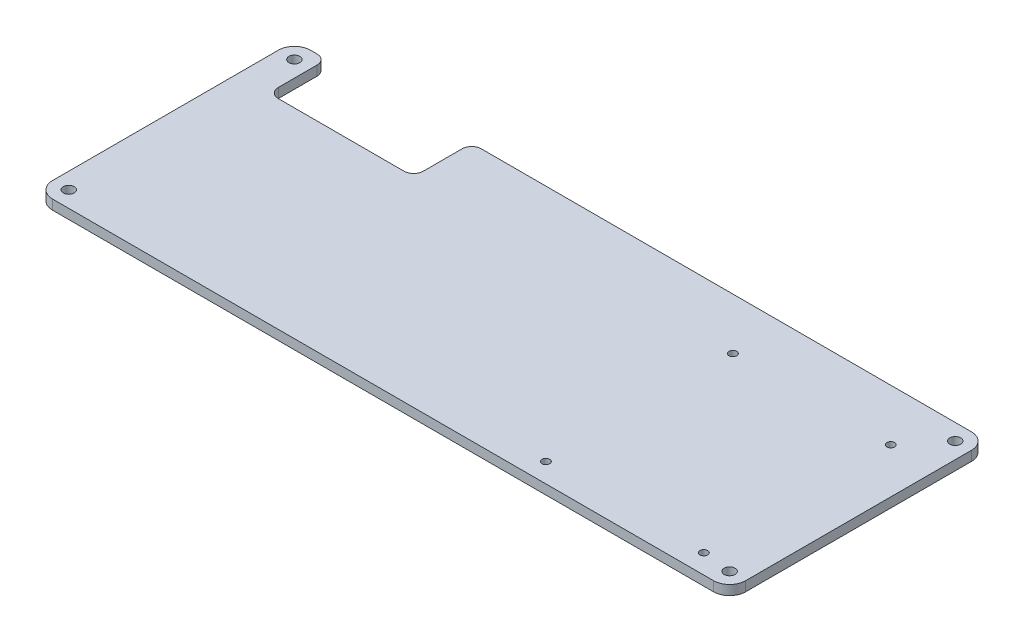
SolidWorks part; units mm, degrees
ref_plane "Front" through (0, 0, 0) normal (0, 0, 1) x (1, 0, 0)
ref_plane "Top" through (0, 0, 0) normal (0, 1, 0) x (1, 0, 0)
ref_plane "Right" through (0, 0, 0) normal (1, 0, 0) x (0, 0, -1)
sketch "Esquisse1" plane through (0, 0, 0) normal (0, 1, 0) x (1, 0, 0)
  line L1 (0, 0) -> (215, 0)
  line L2 (0, 0) -> (0, 80)
  line L3 (0, 80) -> (215, 80)
  line L4 (215, 0) -> (215, 80)
  dimension "D1" = 215
  dimension "D2" = 80
extrude "Boss.-Extru.1" add sketch "Esquisse1" along normal blind 3
fillet "Congé1" radius 5 4 edges at (0, 1.5, -80) (0, 1.5, 0) (215, 1.5, -80) (215, 1.5, 0)
sketch "Esquisse2" plane through (0, 3, 0) normal (0, 1, 0) x (1, 0, 0)
  line L0 (0, 75) -> (0, 5) construction
  line L1 (210, 80) -> (5, 80) construction
  line L2 (5, 0) -> (210, 0) construction
  line L3 (215, 5) -> (215, 75) construction
  line L5 (10, 80) -> (55, 80)
  line L6 (10, 80) -> (10, 62)
  line L7 (10, 62) -> (55, 62)
  line L8 (55, 80) -> (55, 62)
  circle A0 centre (5, 75) radius 1
  circle A1 centre (210, 75) radius 1
  circle A2 centre (210, 5) radius 1
  circle A3 centre (5, 5) radius 1
  dimension "D9" = 2
  dimension "D10" = 2
  dimension "D11" = 2
  dimension "D12" = 2
  dimension "D1" = 5
  dimension "D2" = 5
  dimension "D3" = 5
  dimension "D4" = 5
  dimension "D5" = 5
  dimension "D6" = 5
  dimension "D7" = 5
  dimension "D8" = 5
  dimension "D13" = 10
  dimension "D14" = 45
  dimension "D15" = 18
extrude "Enlèv. mat.-Extru.1" cut sketch "Esquisse2" against normal through all
hole_wizard "Dégagement M31" positions "Esquisse3" profile "Esquisse4" hole size "M3" standard "ISO"
sketch "Esquisse3" plane through (0, 3, 0) normal (0, 1, 0) x (1, 0, 0)
  point P0 (210, 5)
  point P3 (5, 5)
  point P6 (5, 75)
  point P9 (210, 75)
sketch "Esquisse4" plane through (210, 3, -5) normal (1, 0, 0) x (0, 0, 1)
  line L0 (0, 0) -> (0, 11.0215)
  line L1 (0, 11.0215) -> (1.7, 10)
  line L2 (1.7, 10) -> (1.7, 0)
  line L5 (1.7, 0) -> (0, 0)
  line L10 (0, 11.0215) -> (-1.7, 10) construction
  line L11 (0, -6.35) -> (0, 107.95) construction
  dimension "Diamètre du perçage" = 3.4
  dimension "Profondeur du perçage" = 10
  dimension "Angle de pointe" = 118
fillet "Congé2" radius 3 4 edges at (55, 1.5, -62) (55, 1.5, -80) (10, 1.5, -80) (10, 1.5, -62)
sketch "Esquisse5" plane through (0, 3, 0) normal (0, 1, 0) x (1, 0, 0)
  line L0 (215, 5) -> (215, 75) construction
  line L1 (5, 0) -> (210, 0) construction
  circle A0 centre (201, 6) radius 1.5
  circle A1 centre (201, 64) radius 1.5
  circle A2 centre (152, 64) radius 1.5
  circle A3 centre (152, 6) radius 1.5
  dimension "D1" = 14
  dimension "D7" = 3
  dimension "D8" = 3
  dimension "D9" = 3
  dimension "D10" = 3
  dimension "D2" = 6
  dimension "D3" = 58
  dimension "D4" = 49
  dimension "D5" = 58
  dimension "D6" = 49
  dimension "D11" = 14
  dimension "D12" = 6
hole_wizard "Dégagement M21" positions "Esquisse7" profile "Esquisse8" hole size "M2" standard "ISO" end condition through all
sketch "Esquisse7" plane through (0, 3, 0) normal (0, 1, 0) x (1, 0, 0)
  point P0 (201, 64)
  point P3 (152, 64)
  point P6 (152, 6)
  point P9 (201, 6)
sketch "Esquisse8" plane through (201, 3, -64) normal (1, 0, 0) x (0, 0, 1)
  line L0 (0, 0) -> (0, 3)
  line L1 (0, 3) -> (1.2, 3)
  line L2 (1.2, 3) -> (1.2, 0)
  line L5 (1.2, 0) -> (0, 0)
  line L11 (0, -6.35) -> (0, 107.95) construction
  dimension "Diamètre du perçage jusqu'au prochain" = 2.4
  dimension "Profondeur du perçage jusqu'au prochain" = 3
